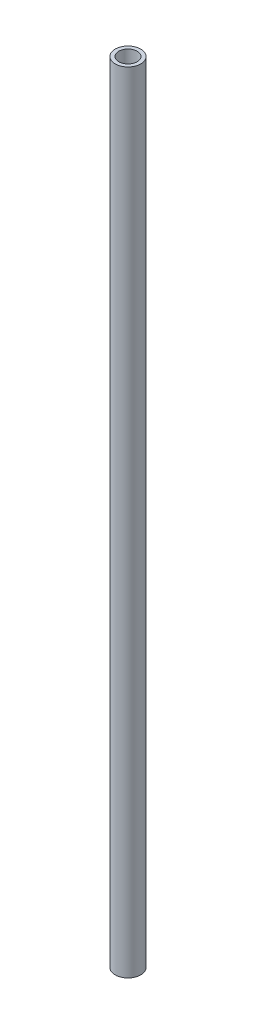
SolidWorks part; units mm, degrees
ref_plane "Front Plane" through (0, 0, 0) normal (0, 0, 1) x (1, 0, 0)
ref_plane "Top Plane" through (0, 0, 0) normal (0, 1, 0) x (1, 0, 0)
ref_plane "Right Plane" through (0, 0, 0) normal (1, 0, 0) x (0, 0, -1)
sketch "Sketch1" plane through (0, 0, 0) normal (0, 1, 0) x (1, 0, 0)
  circle A0 centre (0, 0) radius 2.5
  circle A1 centre (0, 0) radius 3.5
  dimension "D1" = 5
  dimension "D2" = 7
extrude "Boss-Extrude1" add sketch "Sketch1" along normal mid plane 215
